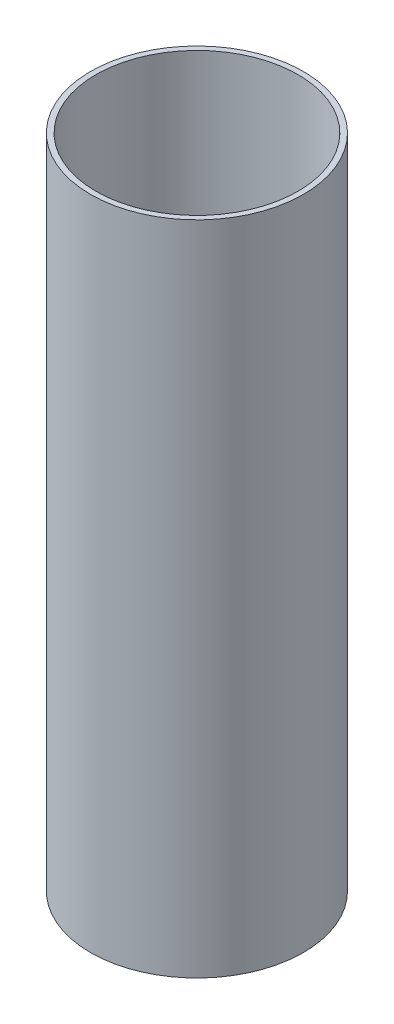
SolidWorks part; units mm, degrees
material "PVC Rigid"
ref_plane "Front Plane" through (0, 0, 0) normal (0, 0, 1) x (1, 0, 0)
ref_plane "Top Plane" through (0, 0, 0) normal (0, 1, 0) x (1, 0, 0)
ref_plane "Right Plane" through (0, 0, 0) normal (1, 0, 0) x (0, 0, -1)
sketch "Sketch1" plane through (0, 0, 0) normal (0, 1, 0) x (1, 0, 0)
  circle A0 centre (0, 0) radius 93.6625
  circle A1 centre (0, 0) radius 88.9
  dimension "D1" = 187.325
  dimension "D2" = 177.8
extrude "Boss-Extrude1" add sketch "Sketch1" along normal mid plane 577.596
